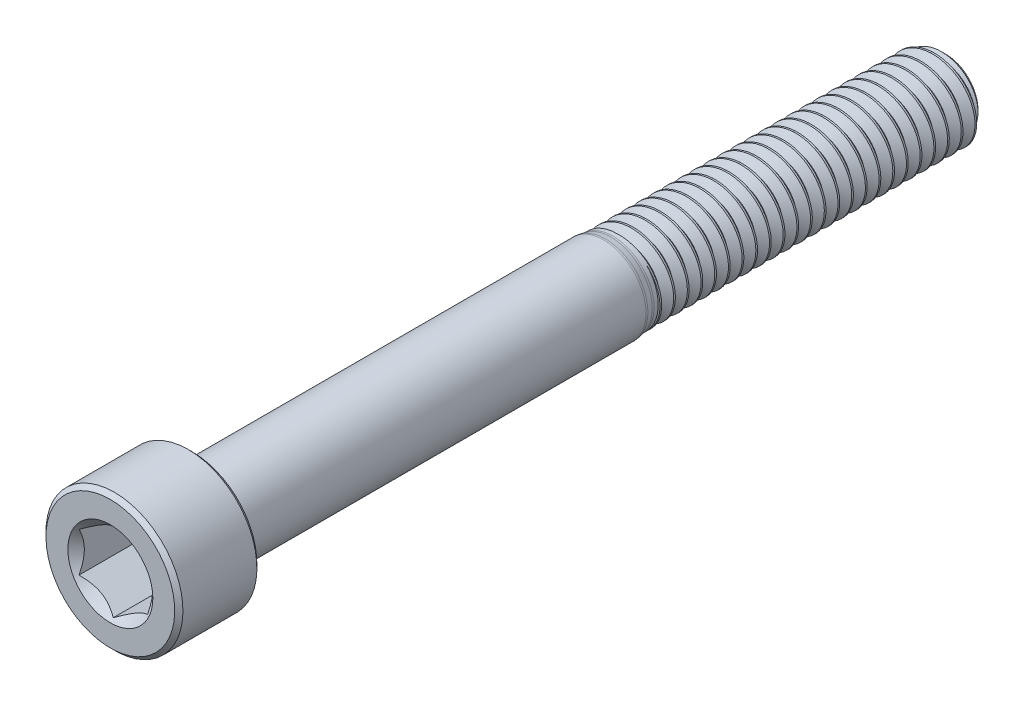
SolidWorks part; units mm, degrees
ref_plane "Front Plane" through (0, 0, 0) normal (0, 0, 1) x (1, 0, 0)
ref_plane "Top Plane" through (0, 0, 0) normal (0, 1, 0) x (1, 0, 0)
ref_plane "Right Plane" through (0, 0, 0) normal (1, 0, 0) x (0, 0, -1)
sketch "Sketch1" plane through (0, 0, 0) normal (1, 0, 0) x (0, 0, -1)
  line L0 (-30.5, 0) -> (30.5, 0) construction
  line L1 (30.5, 0) -> (30.5, 2.3505) construction
  line L2 (30.5, 2.3505) -> (29.8505, 3) construction
  line L3 (29.8505, 3) -> (29.75, 3) construction
  line L4 (29.75, 3) -> (-24.5, 3) construction
  line L5 (-24.5, 3) -> (-24.5, 5) construction
  line L6 (-24.5, 5) -> (-30.5, 5) construction
  line L7 (-30.5, 5) -> (-30.5, 0) construction
  line L8 (30.5, 2.3505) -> (30.5, 3) construction
  line L9 (30.4375, 3.1083) -> (30.9375, 2.2422) construction
  line L10 (30.9375, 2.2422) -> (31.4375, 3.1083) construction
  line L11 (31.4375, 3.1083) -> (30.4375, 3.1083) construction
  line L12 (30.9375, 3.1083) -> (30.9375, 3) construction
  line L13 (30.9375, 2.2422) -> (30.9375, 2.3505) construction
  line L14 (30.875, 2.3505) -> (31, 2.3505) construction
  line L15 (30.5, 3) -> (31.375, 3) construction
  line L16 (30.4687, 3.0541) -> (31.4063, 3.0541) construction
  line L17 (30.5, 0) -> (30.5, -3) construction
  line L18 (-24.8, 5) -> (-24.5, 4.7) construction
  line L19 (-30.2, 5) -> (-30.5, 4.7) construction
  line L20 (-24.5, 3) -> (-24.5, 0) construction
  line L21 (-24.5, 1.5) -> (-6.1667, 1.5) construction
  line L22 (-6.1667, 1.5) -> (12.1667, 1.5) construction
  line L23 (12.1667, 1.5) -> (30.5, 1.5) construction
  line L24 (-6.1667, 1.5) -> (-6.1667, 3) construction
  line L25 (-6.1667, 3) -> (-6.1667, 5) construction
  line L26 (12.1667, 1.5) -> (12.1667, 5) construction
  point P0 (-30.5, 2.5)
  point P3 (28, 3)
  point P4 (0, 0)
  point P18 (12.1667, 3)
  point P22 (30.9375, 2.3505)
  point P24 (29.75, 3)
  point P25 (30.9375, 3)
  point P28 (30.9375, 3.0541)
  point P29 (28, -3)
  point P30 (-6.1667, 3)
  point P31 (-27.5, 5)
  point P37 (-25.55, 5)
  point P38 (-30.05, 5)
  point P45 (-6.1667, 1.5)
  point P46 (12.1667, 1.5)
  point P49 (6.5, 3)
  dimension "D1" = 45
  dimension "D2" = 0.125
  dimension "D7" = 0.3
  dimension "D8" = 0.3
  dimension "D9" = 0.3
  dimension "D10" = 0.15
  dimension "D11" = 0.75
  dimension "Drive Size" = 5
  dimension "Head Diameter" = 10
  dimension "Head Height" = 6
  dimension "Thread Pitch" = 1
  dimension "Thread Dia" = 6
  dimension "Length" = 55
  dimension "D12" = 0.75
  dimension "D4" = 2.5
  dimension "Minimum Thread Length" = 24
  dimension "D3" = 31
sketch "Sketch2" plane through (0, 0, 0) normal (1, 0, 0) x (0, 0, -1)
  line L0 (-30.5, 0) -> (-30.5, 4.7)
  line L1 (-30.2, 5) -> (-24.8, 5)
  line L2 (-24.5, 4.7) -> (-24.5, 3.4083)
  line L4 (29.8505, 3) -> (30.5, 2.3505)
  line L5 (30.5, 2.3505) -> (30.5, 0)
  line L6 (-24.5, 5) -> (-30.5, 5) construction
  line L7 (30.5, 0) -> (-30.5, 0)
  line L8 (-30.2, 5) -> (-30.5, 4.7) construction
  line L10 (-30.2, 5) -> (-30.5, 4.7)
  line L14 (-24.8, 5) -> (-24.5, 4.7) construction
  line L16 (-24.8, 5) -> (-24.5, 4.7)
  line L17 (-24.5, 3) -> (-24.5, 5) construction
  line L18 (-24.2, 3.1083) -> (5.5069, 3.1083)
  line L19 (6.1989, 3) -> (29.8505, 3)
  line L20 (29.75, 3) -> (-24.5, 3) construction
  line L21 (5.6532, 3.0938) -> (6.0526, 3.0144)
  line L22 (31.4375, 3.1083) -> (30.4375, 3.1083) construction
  arc A1 (-24.5, 3.4083) -> (-24.2, 3.1083) centre (-24.2, 3.4083) ccw
  arc A2 (5.5069, 3.1083) -> (5.6532, 3.0938) centre (5.5069, 2.3583) cw
  arc A3 (6.0526, 3.0144) -> (6.1989, 3) centre (6.1989, 3.75) ccw
  point P39 (6.125, 3)
  dimension "D3" = 0.3
  dimension "D6" = 0.75
  dimension "D4" = 11.25
  dimension "D5" = 0.375
revolve "Revolve1" add sketch "Sketch2" angle 360 about L7
sketch "Sketch3" plane through (0, 0, 30.5) normal (0, 0, 1) x (1, 0, 0)
  line L1 (2.5, -1.4434) -> (2.5, 1.4434)
  line L2 (2.5, 1.4434) -> (0, 2.8868)
  line L3 (0, 2.8868) -> (-2.5, 1.4434)
  line L4 (-2.5, 1.4434) -> (-2.5, -1.4434)
  line L5 (-2.5, -1.4434) -> (0, -2.8868)
  line L6 (0, -2.8868) -> (2.5, -1.4434)
  circle A0 centre (0, 0) radius 2.5 construction
  circle A1 centre (0, 0) radius 5 construction
  circle A2 centre (0, 0) radius 5 construction
  circle A3 centre (0, 0) radius 2.8868 construction
  dimension "D1" = 5.7735
extrude "Cut-Extrude1" cut sketch "Sketch3" against normal offset from surface (5 mm away) 1 up to face at (0, 4.7, 24.5)
sketch "Sketch4" plane through (0, 0, 30.5) normal (0, 0, 1) x (1, 0, 0)
  circle A0 centre (0, 0) radius 3.1033
  dimension "D1" = 6.2065
extrude "Cut-Extrude2" cut sketch "Sketch4" against normal up to vertex (3 mm away) draft 45 up to point (0, 5, 27.5)
sketch "Sketch11" plane through (0, 0, 0) normal (1, 0, 0) x (0, 0, -1)
  line L0 (-30.5, 0) -> (30.5, 0) construction
  line L1 (-30.5, 0) -> (30.5, 0) construction
  line L2 (-21.7875, 0) -> (-21.7875, 3) construction
  line L3 (29.75, 3) -> (-24.5, 3) construction
  line L4 (2.7944, 0) -> (2.7944, 3) construction
  point P2 (-21.7875, 0)
  point P3 (2.7944, 0)
  dimension "D1" = 2.7125
  dimension "D2" = 2.7125
sketch "Sketch6" plane through (0, 0, -30.5) normal (0, 0, -1) x (-1, 0, 0)
  circle A0 centre (0, 0) radius 3
curve "Helix/Spiral1" pitch 1 height 25 radius 3 centre (0, 0, -30.5) axis (0, 0, 1) start towards (0, 1, 0)
sketch "Sketch10" plane through (0, 0, 0) normal (1, 0, 0) x (0, 0, -1)
  line L0 (6.5, -3) -> (6.5, 3)
  line L2 (-30.5, 0) -> (30.5, 0) construction
  point P3 (6.5, 0)
split "Split1" trim tools "Sketch10" bodies to split 106 resulting bodies 114 115
sketch "Sketch7" plane through (0, 0, 0) normal (1, 0, 0) x (0, 0, -1)
  line L0 (30.4687, 3.0541) -> (31.4063, 3.0541)
  line L1 (31.4063, 3.0541) -> (31, 2.3505)
  line L2 (31, 2.3505) -> (30.875, 2.3505)
  line L3 (30.875, 2.3505) -> (30.4687, 3.0541)
sweep "Cut-Sweep1" cut profiles "Sketch7" path "Helix/Spiral1" align with end faces yes
sketch "Sketch8" plane through (0, 0, 0) normal (1, 0, 0) x (0, 0, -1)
  line L0 (-24.5, 0) -> (-24.5, 3)
  line L2 (-24.5, 3) -> (6.5, 3)
  line L4 (6.5, 3) -> (8.2321, 0)
  line L5 (8.2321, 0) -> (-24.5, 0)
  line L6 (29.75, 3) -> (-24.5, 3) construction
  line L7 (-30.5, 0) -> (30.5, 0) construction
  dimension "D1" = 60
  dimension "D2" = 24
revolve "Revolve2" add sketch "Sketch8" angle 360 about L5
equation "\"D2@Sketch1\" = \"Thread Pitch@Sketch1\" / 8"
equation "\"D4@Helix/Spiral1\" = \"Thread Pitch@Sketch1\""
equation "\"D7@Sketch1\" = \"Head Height@Sketch1\" * .05"
equation "\"D8@Sketch1\"=\"D7@Sketch1\""
equation "\"D9@Sketch1\"=\"D7@Sketch1\""
equation "\"D10@Sketch1\"=\"D7@Sketch1\"/2"
equation "\"D11@Sketch1\"=\"D10@Sketch1\"*5"
equation "\"D4@Sketch1\"=\"Thread Pitch@Sketch1\"*2.5"
equation "\"D12@Sketch1\"=\"Thread Pitch@Sketch1\"*.75"
equation "\"D3@Helix/Spiral1\"=\"Minimum Thread Length@Sketch1\"+\"Thread Pitch@Sketch1\""
equation "\"D2@Sketch8\"=\"Minimum Thread Length@Sketch1\""
equation "\"D3@Sketch2\"=\"Thread Dia@Sketch1\"*0.05"
equation "\"D5@Sketch2\"=\"D12@Sketch1\"*0.5"
equation "\"D6@Sketch2\"=\"Thread Dia@Sketch1\"*0.125"
equation "\"D1@Sketch11\"=\"D3@Sketch1\"*0.0875"
equation "\"D2@Sketch11\"=\"D1@Sketch11\""
equation "\"D1@Sketch4\"=\"D1@Sketch3\"*1.075"
